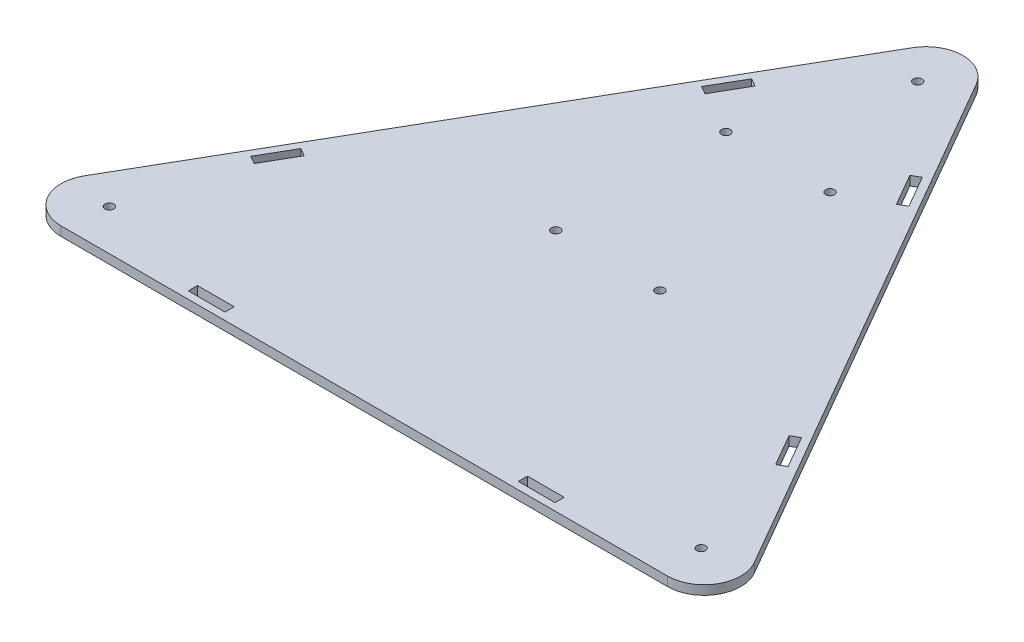
SolidWorks part; units mm, degrees
ref_plane "Front Plane" through (0, 0, 0) normal (0, 0, 1) x (1, 0, 0)
ref_plane "Top Plane" through (0, 0, 0) normal (0, 1, 0) x (1, 0, 0)
ref_plane "Right Plane" through (0, 0, 0) normal (1, 0, 0) x (0, 0, -1)
sketch "Sketch1" plane through (0, 0, 0) normal (0, 1, 0) x (1, 0, 0)
  line L1 (0, 146.647) -> (-127, -73.3235)
  line L2 (-127, -73.3235) -> (127, -73.3235)
  line L3 (127, -73.3235) -> (0, 146.647)
  circle A0 centre (0, 0) radius 73.3235 construction
  dimension "D1" = 254
extrude "Boss-Extrude1" add sketch "Sketch1" along normal blind 3.175
sketch "Sketch2" plane through (0, 3.175, 0) normal (0, 1, 0) x (1, 0, 0)
  line L0 (0, -59.3535) -> (0, -73.3235)
  line L1 (-82.55, -73.3235) -> (82.55, -73.3235)
  line L2 (-82.55, -73.3235) -> (-82.55, -59.3535)
  line L3 (-82.55, -59.3535) -> (82.55, -59.3535)
  line L4 (82.55, -73.3235) -> (82.55, -59.3535)
  line L5 (-127, -73.3235) -> (127, -73.3235) construction
  line L6 (0, -61.8935) -> (0, 1.1065)
  line L7 (-38.1, 1.1065) -> (38.1, 1.1065)
  line L8 (-38.1, 1.1065) -> (-38.1, -61.8935)
  line L9 (-38.1, -61.8935) -> (38.1, -61.8935)
  line L10 (38.1, 1.1065) -> (38.1, -61.8935)
  line L11 (-63.5, 36.6617) -> (-51.4016, 29.6767)
  line L12 (-104.775, -34.8287) -> (-22.225, 108.1521)
  line L13 (-104.775, -34.8287) -> (-92.6766, -41.8137)
  line L14 (-92.6766, -41.8137) -> (-10.1266, 101.1671)
  line L15 (-22.225, 108.1521) -> (-10.1266, 101.1671)
  line L16 (63.5, 36.6617) -> (51.4016, 29.6767)
  line L17 (22.225, 108.1521) -> (104.775, -34.8287)
  line L18 (22.225, 108.1521) -> (10.1266, 101.1671)
  line L19 (10.1266, 101.1671) -> (92.6766, -41.8137)
  line L20 (104.775, -34.8287) -> (92.6766, -41.8137)
  line L23 (0, 146.647) -> (-127, -73.3235) construction
  line L24 (127, -73.3235) -> (0, 146.647) construction
  line L25 (-104.775, -34.8287) -> (-82.55, -73.3235)
  line L26 (104.775, -34.8287) -> (82.55, -73.3235)
  line L27 (-22.225, 108.1521) -> (22.225, 108.1521)
  circle A0 centre (-102.4613, -59.1561) radius 1.524
  circle A1 centre (102.4613, -59.1561) radius 1.524
  circle A2 centre (0, 118.3121) radius 1.524
  dimension "D11" = 3.048
  dimension "D13" = 3.048
  dimension "D15" = 3.048
  dimension "D1" = 165.1
  dimension "D2" = 13.97
  dimension "D3" = 63
  dimension "D4" = 76.2
  dimension "D5" = 11.43
  dimension "D6" = 165.1
  dimension "D7" = 13.97
  dimension "D8" = 165.1
  dimension "D9" = 13.97
  dimension "D10" = 10.16
  dimension "D12" = 10.16
  dimension "D14" = 10.16
extrude "Cut-Extrude2" cut sketch "Sketch2" against normal through all contours A2 | A0 | A1 region at (-102.4613, 3.175, 59.1561) region at (102.4613, 3.175, 59.1561) region at (0, 3.175, -118.3121)
fillet "Fillet1" radius 12.7 3 edges at (-127, 1.5875, 73.3235) (0, 1.5875, -146.647) (127, 1.5875, 73.3235)
sketch "Sketch3" plane through (0, 3.175, 0) normal (0, 1, 0) x (1, 0, 0)
  line L0 (-10.9985, 127.597) -> (-116.0015, -54.2735) construction
  line L1 (116.0015, -54.2735) -> (10.9985, 127.597) construction
  line L2 (-105.003, -73.3235) -> (105.003, -73.3235) construction
  line B0 (61.3003, 35.3917) -> (58.5507, 33.8042)
  line B1 (103.0007, -43.1854) -> (105.7503, -41.5979)
  line B2 (103.0007, -43.1854) -> (14.1007, 110.7939)
  line B3 (14.1007, 110.7939) -> (16.8503, 112.3814)
  line B4 (105.7503, -41.5979) -> (16.8503, 112.3814)
  line B5 (93.0503, -19.6009) -> (90.3007, -21.1884)
  line B6 (93.0503, -19.6009) -> (86.7003, -8.6023)
  line B7 (86.7003, -8.6023) -> (83.9507, -10.1898)
  line B8 (90.3007, -21.1884) -> (83.9507, -10.1898)
  line B9 (35.9003, 79.3858) -> (33.1507, 77.7983)
  line B10 (35.9003, 79.3858) -> (29.5503, 90.3844)
  line B11 (29.5503, 90.3844) -> (26.8007, 88.7969)
  line B12 (33.1507, 77.7983) -> (26.8007, 88.7969)
  line B13 (105.7503, -41.5979) -> (107.95, -40.3279)
  line B14 (105.7503, -41.5979) -> (16.8503, 112.3814)
  line B15 (16.8503, 112.3814) -> (19.05, 113.6514)
  line B16 (107.95, -40.3279) -> (19.05, 113.6514)
  line B17 (0, -70.7835) -> (0, -67.6085)
  line B18 (-88.9, -67.6085) -> (-88.9, -70.7835)
  line B19 (-88.9, -67.6085) -> (88.9, -67.6085)
  line B20 (88.9, -67.6085) -> (88.9, -70.7835)
  line B21 (-88.9, -70.7835) -> (88.9, -70.7835)
  line B22 (-63.5, -70.7835) -> (-63.5, -67.6085)
  line B23 (-63.5, -70.7835) -> (-50.8, -70.7835)
  line B24 (-50.8, -70.7835) -> (-50.8, -67.6085)
  line B25 (-63.5, -67.6085) -> (-50.8, -67.6085)
  line B26 (50.8, -70.7835) -> (50.8, -67.6085)
  line B27 (50.8, -70.7835) -> (63.5, -70.7835)
  line B28 (63.5, -70.7835) -> (63.5, -67.6085)
  line B29 (50.8, -67.6085) -> (63.5, -67.6085)
  line B30 (-88.9, -70.7835) -> (-88.9, -73.3235)
  line B31 (-88.9, -70.7835) -> (88.9, -70.7835)
  line B32 (88.9, -70.7835) -> (88.9, -73.3235)
  line B33 (-88.9, -73.3235) -> (88.9, -73.3235)
  line B34 (-61.3003, 35.3917) -> (-58.5507, 33.8042)
  line B35 (-14.1007, 110.7939) -> (-16.8503, 112.3814)
  line B36 (-14.1007, 110.7939) -> (-103.0007, -43.1854)
  line B37 (-103.0007, -43.1854) -> (-105.7503, -41.5979)
  line B38 (-16.8503, 112.3814) -> (-105.7503, -41.5979)
  line B39 (-29.5503, 90.3844) -> (-26.8007, 88.7969)
  line B40 (-29.5503, 90.3844) -> (-35.9003, 79.3858)
  line B41 (-35.9003, 79.3858) -> (-33.1507, 77.7983)
  line B42 (-26.8007, 88.7969) -> (-33.1507, 77.7983)
  line B43 (-86.7003, -8.6023) -> (-83.9507, -10.1898)
  line B44 (-86.7003, -8.6023) -> (-93.0503, -19.6009)
  line B45 (-93.0503, -19.6009) -> (-90.3007, -21.1884)
  line B46 (-83.9507, -10.1898) -> (-90.3007, -21.1884)
  line B47 (-16.8503, 112.3814) -> (-19.05, 113.6514)
  line B48 (-16.8503, 112.3814) -> (-105.7503, -41.5979)
  line B49 (-105.7503, -41.5979) -> (-107.95, -40.3279)
  line B50 (-19.05, 113.6514) -> (-107.95, -40.3279)
sketch_block_instance "Block3-1"
sketch_block "Block3" parameters "D1"=177.8, "D2"=3.175, "D3"=25.4, "D4"=25.4, "D5"=12.7, "D6"=12.7, "D7"=2.54
sketch_block_instance "Block3-2"
sketch_block_instance "Block3-3"
extrude "Cut-Extrude3" cut sketch "Sketch3" against normal through all contours B38 B41 B36 B39 | B38 B45 B36 B43 | B21 B24 B19 B22 | B21 B28 B19 B26 | B4 B7 B2 B5 | B4 B11 B2 B9 region at (88.5005, 3.175, 14.8954) region at (31.3505, 3.175, -84.0913) region at (-57.15, 3.175, 69.196) region at (57.15, 3.175, 69.196) region at (-31.3505, 3.175, -84.0913) region at (-88.5005, 3.175, 14.8954)
sketch "Sketch4" plane through (0, 3.175, 0) normal (0, 1, 0) x (1, 0, 0)
  line L2 (0, 133.947) -> (0, -73.3235) construction
  line L3 (-20.32, 72.2265) -> (20.32, 72.2265)
  line L4 (-20.32, 72.2265) -> (-20.32, 8.7265)
  line L5 (-20.32, 8.7265) -> (20.32, 8.7265)
  line L6 (20.32, 72.2265) -> (20.32, 8.7265)
  line L7 (-105.003, -73.3235) -> (105.003, -73.3235) construction
  circle A0 centre (-18.034, 69.9405) radius 1.524
  circle A1 centre (18.034, 69.9405) radius 1.524
  circle A2 centre (-18.034, 11.0125) radius 1.524
  circle A3 centre (18.034, 11.0125) radius 1.524
  arc A4 (10.9985, 127.597) -> (-10.9985, 127.597) centre (0, 121.247) ccw construction
  point P21 (0, 72.2265)
  dimension "D3" = 3.048
  dimension "D4" = 2.286
  dimension "D5" = 2.286
  dimension "D6" = 2.286
  dimension "D7" = 2.286
  dimension "D8" = 2.286
  dimension "D9" = 2.286
  dimension "D10" = 2.286
  dimension "D11" = 2.286
  dimension "D1" = 63.5
  dimension "D2" = 40.64
extrude "Cut-Extrude4" cut sketch "Sketch4" against normal through all contours A0 | A1 | A3 | A2 region at (-18.034, 3.175, -69.9405) region at (18.034, 3.175, -69.9405) region at (-18.034, 3.175, -11.0125) region at (18.034, 3.175, -11.0125)
